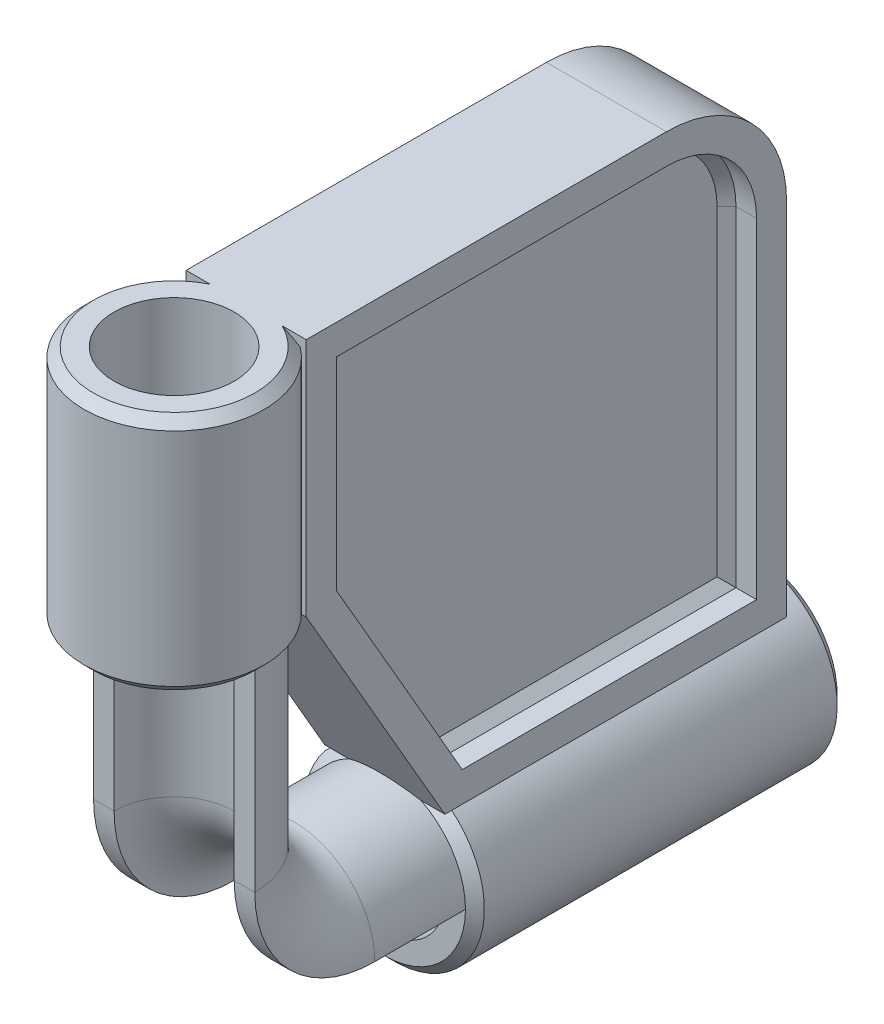
SolidWorks part; units mm, degrees
ref_plane "Front Plane" through (0, 0, 0) normal (1, 0, 0) x (0, 1, 0)
ref_plane "Top Plane" through (0, 0, 0) normal (0, 0, 1) x (0, 1, 0)
ref_plane "Right Plane" through (0, 0, 0) normal (0, 1, 0) x (-1, 0, 0)
sketch "Sketch1" plane through (0, 0, 0) normal (1, 0, 0) x (0, 1, 0)
  line L0 (-25.4, 10.7353) -> (0, 25.4)
  line L1 (-25.4, -25.4) -> (25.4, -25.4)
  line L2 (-25.4, -25.4) -> (-25.4, 10.7353)
  line L3 (0, 25.4) -> (25.4, 25.4)
  line L4 (25.4, -25.4) -> (25.4, 25.4)
  line L5 (0, -55) -> (0, 55) construction
  line L6 (55, 0) -> (-55, 0) construction
  point P0 (0, 0)
  point P10 (25.4, 0)
  dimension "D1" = 50.8
  dimension "D2" = 50.8
  dimension "D3" = 30
  dimension "D4" = 25.4
extrude "Boss-Extrude1" add sketch "Sketch1" along normal mid plane 12.7
fillet "Fillet1" radius 12.7 1 edges at (0, 25.4, -25.4)
sketch "Sketch3" plane through (6.35, 0, 0) normal (1, 0, 0) x (0, 1, 0)
  line L10 (-22.225, -22.225) -> (12.7, -22.225)
  line L11 (22.225, -12.7) -> (22.225, 22.225)
  line L12 (22.225, 22.225) -> (0.8507, 22.225)
  line L13 (0.8507, 22.225) -> (-22.225, 8.9022)
  line L14 (-22.225, 8.9022) -> (-22.225, -22.225)
  line L15 (-22.225, -22.225) -> (12.7, -22.225)
  line L16 (22.225, -12.7) -> (22.225, 22.225)
  line L17 (22.225, 22.225) -> (0.8507, 22.225)
  line L18 (0.8507, 22.225) -> (-22.225, 8.9022)
  line L19 (-22.225, 8.9022) -> (-22.225, -22.225)
  arc A2 (12.7, -22.225) -> (22.225, -12.7) centre (12.7, -12.7) ccw
  arc A3 (12.7, -22.225) -> (22.225, -12.7) centre (12.7, -12.7) ccw
  dimension "D1" = 3.175
extrude "Cut-Extrude2" cut sketch "Sketch3" against normal blind 3.175
mirror "Mirror1" about plane through (0, 0, 0) normal (1, 0, 0) of "Cut-Extrude2"
sketch "Sketch4" plane through (0, 0, -25.4) normal (0, 0, -1) x (1, 0, 0)
  line L0 (0, -27.94) -> (0, 27.94) construction
  line L1 (6.35, -25.4) -> (-6.35, -25.4) construction
  circle A0 centre (0, 33.02) radius 9.525
  circle A1 centre (0, 33.02) radius 6.35
  dimension "D1" = 19.05
  dimension "D2" = 12.7
  dimension "D3" = 58.42
extrude "Boss-Extrude2" add sketch "Sketch4" against normal up to vertex (36.1353 mm away) and the other way blind 3.175 up to point (6.35, -25.4, 10.7353)
sketch "Sketch5" plane through (0, 25.4, 0) normal (0, 1, 0) x (-1, 0, 0)
  line L0 (0, 29.6863) -> (0, -29.6863) construction
  line L1 (-5.715, -25.4) -> (5.715, -25.4) construction
  circle A0 centre (0, 33.02) radius 9.525
  circle A1 centre (0, 33.02) radius 6.35
  dimension "D1" = 19.05
  dimension "D2" = 12.7
  dimension "D3" = 58.42
extrude "Boss-Extrude3" add sketch "Sketch5" against normal up to surface (25.4 mm away) up to plane "Right Plane"
chamfer "Chamfer2" distance 1 angle 45 4 edges at (0, 0, 42.545) (0, -42.545, 10.7353) (0, -23.495, -28.575) (0, 25.4, 42.545)
sketch "Sketch6" plane through (0, 0, 0) normal (1, 0, 0) x (0, 1, 0)
  line L0 (-26.67, 10.7353) -> (-39.37, 10.7353) construction
  line L1 (-26.67, 10.7353) -> (-39.37, 10.7353) construction
  line L2 (0, 39.37) -> (0, 26.67) construction
  line L3 (0, 39.37) -> (0, 26.67) construction
  line L4 (-20.32, 33.02) -> (0, 33.02)
  line L5 (-33.02, 20.32) -> (-33.02, 10.7353)
  arc A0 (-33.02, 20.32) -> (-20.32, 33.02) centre (-20.32, 20.32) cw
  point P6 (-33.02, 10.7353)
  point P9 (0, 33.02)
  dimension "D1" = 12.7
sketch "Sketch7" plane through (0, 0, 0) normal (0, -1, 0) x (1, 0, 0)
  line L0 (-8.525, 33.02) -> (-6.35, 33.02)
  line L1 (6.35, 33.02) -> (8.525, 33.02)
  line L2 (0, 39.37) -> (0, 26.67) construction
  circle A0 centre (0, 33.02) radius 6.35 construction
  arc A4 (-6.35, 33.02) -> (6.35, 33.02) centre (0, 33.02) ccw
  arc A5 (-8.525, 33.02) -> (8.525, 33.02) centre (0, 33.02) ccw
  arc A6 (3.8225, 25.4) -> (-3.8225, 25.4) centre (0, 33.02) ccw construction
sweep "Sweep3" add profiles "Sketch7" path "Sketch6"
chamfer "Chamfer4" distance 1 angle 45 12 edges at (-3.175, -4.7625, -22.225) (-3.175, 19.4352, -19.4352) (-3.175, 22.225, 4.7625) (-3.175, 11.5379, 22.225) (-3.175, -10.6871, 15.5636) (-3.175, -22.225, -6.6614) (3.175, -10.6871, 15.5636) (3.175, 11.5379, 22.225) (3.175, 22.225, 4.7625) (3.175, 19.4352, -19.4352) (3.175, -4.7625, -22.225) (3.175, -22.225, -6.6614)
